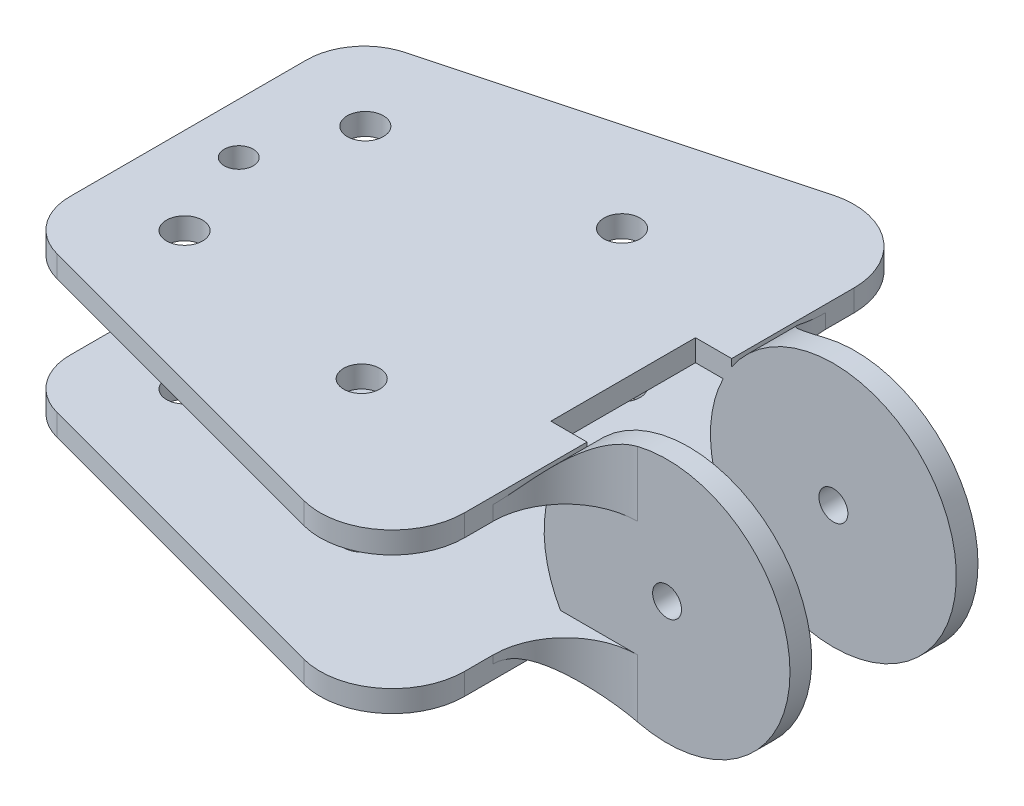
SolidWorks part; units mm, degrees
ref_plane "Alzado" through (0, 0, 0) normal (0, 0, 1) x (1, 0, 0)
ref_plane "Planta" through (0, 0, 0) normal (0, 1, 0) x (1, 0, 0)
ref_plane "Vista lateral" through (0, 0, 0) normal (1, 0, 0) x (0, 0, -1)
sketch "Croquis1" plane through (0, 0, 0) normal (0, 1, 0) x (1, 0, 0)
  line L0 (0, 16.3614) -> (0, -16.3614)
  line L1 (5.9294, -24.0888) -> (69.9294, -41.2375)
  line L2 (80, -33.5101) -> (80, 33.5101)
  line L3 (69.9294, 41.2375) -> (5.9294, 24.0888)
  line L4 (0, 0) -> (80, 0) construction
  line L5 (12, 12.5) -> (12, -12.5) construction
  line L6 (42, 18) -> (42, -18) construction
  line L7 (72, 30) -> (72, -30) construction
  circle A0 centre (12, 12.5) radius 2.5
  circle A1 centre (12, -12.5) radius 2.5
  circle A2 centre (42, 18) radius 2.5
  circle A3 centre (42, -18) radius 2.5
  arc A4 (80, 33.5101) -> (69.9294, 41.2375) centre (72, 33.5101) ccw
  arc A5 (69.9294, -41.2375) -> (80, -33.5101) centre (72, -33.5101) ccw
  arc A6 (0, -16.3614) -> (5.9294, -24.0888) centre (8, -16.3614) ccw
  arc A7 (0, 16.3614) -> (5.9294, 24.0888) centre (8, 16.3614) cw
  circle A8 centre (7, 0) radius 2
  circle A9 centre (72, -30) radius 2
  circle A10 centre (72, 30) radius 2
  point P3 (80, 0)
  point P10 (12, 0)
  point P15 (42, 0)
  point P18 (40, 0)
  point P25 (0, -22.5)
  point P28 (0, 22.5)
  point P35 (72, 0)
  dimension "D2" = 5
  dimension "D9" = 8
  dimension "D11" = 4
  dimension "D1" = 25
  dimension "D3" = 30
  dimension "D4" = 36
  dimension "D5" = 45
  dimension "D6" = 80
  dimension "D7" = 28
  dimension "D8" = 75
  dimension "D10" = 5
  dimension "D12" = 30
  dimension "D13" = 60
extrude "Saliente-Extruir1" add sketch "Croquis1" along normal blind 22
sketch "Croquis2" plane through (0, 0, 0) normal (0, 0, 1) x (1, 0, 0)
  line L0 (0, 22) -> (0, 0) construction
  line L1 (0, 19) -> (80, 19)
  line L2 (0, 19) -> (0, 3)
  line L3 (0, 3) -> (80, 3)
  line L4 (80, 19) -> (80, 3)
  line L5 (80, 22) -> (80, 0) construction
  point P8 (0, 11)
  dimension "D1" = 16
extrude "Cortar-Extruir1" cut sketch "Croquis2" against normal mid plane 100
sketch "Croquis3" plane through (0, 3, 0) normal (0, 1, 0) x (1, 0, 0)
  line L1 (7, -2.3094) -> (9, -1.1547)
  line L2 (9, -1.1547) -> (9, 1.1547)
  line L3 (9, 1.1547) -> (7, 2.3094)
  line L4 (7, 2.3094) -> (5, 1.1547)
  line L5 (5, 1.1547) -> (5, -1.1547)
  line L6 (5, -1.1547) -> (7, -2.3094)
  line L7 (70.8453, -32) -> (73.1547, -32)
  line L8 (73.1547, -32) -> (74.3094, -30)
  line L9 (74.3094, -30) -> (73.1547, -28)
  line L10 (73.1547, -28) -> (70.8453, -28)
  line L11 (70.8453, -28) -> (69.6906, -30)
  line L12 (69.6906, -30) -> (70.8453, -32)
  line L13 (74, 28.8453) -> (74, 31.1547)
  line L14 (74, 31.1547) -> (72, 32.3094)
  line L15 (72, 32.3094) -> (70, 31.1547)
  line L16 (70, 31.1547) -> (70, 28.8453)
  line L17 (70, 28.8453) -> (72, 27.6906)
  line L18 (72, 27.6906) -> (74, 28.8453)
  circle A0 centre (7, 0) radius 2 construction
  circle A1 centre (72, -30) radius 2 construction
  circle A2 centre (72, 30) radius 2 construction
  circle A3 centre (72, 30) radius 2 construction
  circle A4 centre (72, -30) radius 2 construction
  circle A5 centre (7, 0) radius 2 construction
extrude "Saliente-Extruir2" add sketch "Croquis3" along normal blind 16 separate body
sketch "Sketch2" plane through (0, 0, 0) normal (0, 1, 0) x (1, 0, 0)
  line L1 (89.2343, -48.0616) -> (65.161, -48.0616)
  line L2 (89.2343, -48.0616) -> (89.2343, 51.7363)
  line L3 (89.2343, 51.7363) -> (65.161, 51.7363)
  line L4 (65.161, -48.0616) -> (65.161, 51.7363)
extrude "Cut-Extrude3" cut sketch "Sketch2" along normal blind 31
fillet "Fillet2" radius 10 2 edges at (65.161, 20.5, -39.9598) (65.161, 20.5, 39.9598)
fillet "Fillet3" radius 10 2 edges at (65.161, 1.5, 39.9598) (65.161, 1.5, -39.9598)
sketch "Sketch3" plane through (0, 0, 0) normal (0, 0, 1) x (1, 0, 0)
  line L0 (65.161, 22) -> (65.161, 19) construction
  circle A0 centre (79.2314, 11.4652) radius 17
  dimension "D1" = 14.0704
  dimension "D2" = 34
extrude "Boss-Extrude1" add sketch "Sketch3" along normal blind 13 and the other way blind 13
sketch "Sketch4" plane through (0, 0, 0) normal (0, 1, 0) x (1, 0, 0)
  line L0 (96.2314, 13) -> (65.161, 13) construction
  line L1 (60.161, 10) -> (122.1404, 10)
  line L2 (60.161, 10) -> (60.161, -10)
  line L3 (60.161, -10) -> (122.1404, -10)
  line L4 (122.1404, 10) -> (122.1404, -10)
  line L5 (65.161, -13) -> (96.2314, -13) construction
  line L6 (65.161, -26.9276) -> (65.161, 26.9276) construction
  dimension "D1" = 20
  dimension "D2" = 3
  dimension "D3" = 3
  dimension "D4" = 5
extrude "Cut-Extrude4" cut sketch "Sketch4" along normal blind 51 and the other way blind 51
sketch "Sketch5" plane through (0, 0, 13) normal (0, 0, 1) x (1, 0, 0)
  circle A0 centre (79.2314, 11.4652) radius 2
extrude "Cut-Extrude5" cut sketch "Sketch5" against normal blind 51
fillet "Fillet4" radius 10 4 edges at (65.161, 20.003, 13) (65.161, 2.4623, 13) (65.161, 20.003, -13) (65.161, 2.4623, -13)
